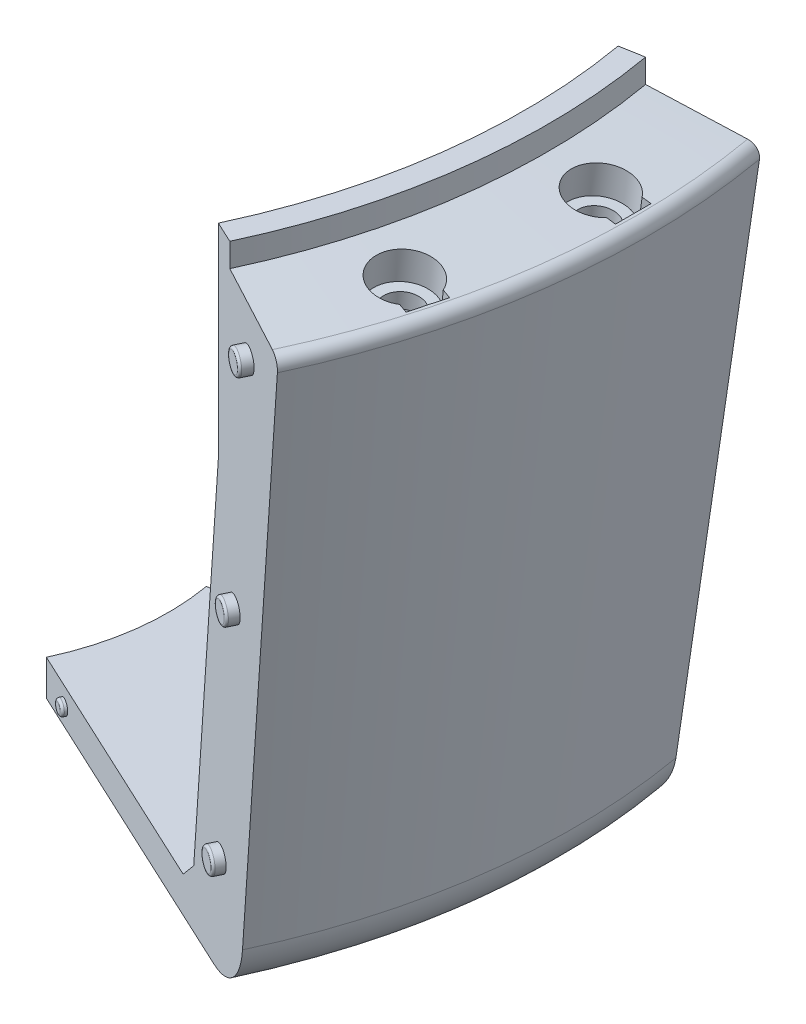
SolidWorks part; units mm, degrees
material "Melamine resin"
ref_plane "Front Plane" through (0, 0, 0) normal (0, 0, 1) x (1, 0, 0)
ref_plane "Top Plane" through (0, 0, 0) normal (0, 1, 0) x (1, 0, 0)
ref_plane "Right Plane" through (0, 0, 0) normal (1, 0, 0) x (0, 0, -1)
sketch "Sketch1" plane through (0, 0, 0) normal (0, 0, 1) x (1, 0, 0)
  line L0 (0, 0) -> (0, 30) construction
  line L3 (10, 0) -> (26.82, 0)
  line L4 (26.82, 0) -> (30.2136, 25.7776)
  line L5 (30.2136, 25.7776) -> (26, 26.3323)
  line L6 (26, 26.3323) -> (26, 27.3323)
  line L7 (26, 27.3323) -> (25, 27.3323)
  line L9 (22.9282, 3) -> (25, 18.7365)
  line L12 (25, 27.3323) -> (25, 18.7365)
  line L14 (21.4282, 3) -> (21.4282, 1.5)
  line L15 (21.4282, 1.5) -> (10, 1.5)
  line L16 (22.9282, 3) -> (21.4282, 3)
  line L17 (10, 1.5) -> (10, 0)
  dimension "D1" = 30
  dimension "D2" = 26
  dimension "D3" = 1
  dimension "D4" = 1.5
  dimension "D5" = 3
  dimension "D6" = 25
  dimension "D7" = 4.25
  dimension "D8" = 97.5
  dimension "D9" = 1
  dimension "D10" = 10
  dimension "D11" = 1.5
revolve "Revolve1" add sketch "Sketch1" angle 10 about L0
ref_plane "Plane1" through (3.8506, 29.2483, 0) normal (0.1305, 0.9914, 0) x (0.9914, -0.1305, 0)
sketch "Sketch2" plane through (3.8506, 29.2483, 0) normal (0.1305, 0.9914, 0) x (0.9914, -0.1305, 0)
  line L0 (25.8905, 0) -> (0, 0) construction
  line L1 (25.8905, -1.5732) -> (4, -1)
  line L2 (4, -1) -> (4, 1)
  line L3 (4, 1) -> (25.8905, 1.5732)
  line L4 (25.8905, 1.5732) -> (25.8905, -1.5732)
  line L5 (25.8905, 0) -> (26.4816, 0) construction
  ellipse E0 centre (-3.3646, 0) end of major axis (-3.3646, -30.2136) minor radius 29.9552 construction
  point P5 (26.5905, 0)
  point P8 (4, 0)
  dimension "D1" = 2
  dimension "D2" = 3
  dimension "D3" = 0.7
  dimension "D4" = 3.1464
  dimension "D5" = 4
extrude "Cut-Extrude1" cut sketch "Sketch2" against normal blind 19 from offset 2 offset against normal yes
pattern_circular "CirPattern1" count 2 every 15 about axis through (0, 0, 0) along (0, 1, 0) of "Cut-Extrude1"
sketch "Sketch3" plane through (3.8506, 29.2483, 0) normal (0.1305, 0.9914, 0) x (0.9914, -0.1305, 0)
  line L0 (0, 0) -> (27.8102, 0) construction
  circle A0 centre (24.5905, 0) radius 1.25
  ellipse E0 centre (-3.3646, 0) end of major axis (-3.3646, -30.2136) minor radius 29.9552 construction
  point P6 (26.5905, 0)
  dimension "D1" = 2.5
  dimension "D2" = 2
extrude "Cut-Extrude2" cut sketch "Sketch3" against normal blind 1.3
pattern_circular "CirPattern2" count 2 every 15 about axis through (0, 27.3323, 0) along (0, -1, 0) of "Cut-Extrude2"
sketch "Sketch4" plane through (3.6809, 27.9594, 0) normal (0.1305, 0.9914, 0) x (0.9914, -0.1305, 0)
  circle A0 centre (24.5905, 0) radius 0.75
  dimension "D1" = 1.5
extrude "Cut-Extrude3" cut sketch "Sketch4" against normal blind 19
pattern_circular "CirPattern3" count 2 every 15 about axis through (0, 27.3323, 0) along (0, -1, 0) of "Cut-Extrude3"
sketch "Sketch20" plane through (3.6809, 27.9594, 0) normal (0.1305, 0.9914, 0) x (0.9914, -0.1305, 0)
  circle A0 centre (24.5905, 0) radius 0.7
  dimension "D1" = 1.4
extrude "Cut-Extrude10" cut sketch "Sketch20" against normal blind 7.4 from offset 15 offset against normal yes
pattern_circular "CirPattern14" count 2 over 15 about axis through (0, 0, 0) along (0, -1, 0) of "Cut-Extrude10"
ref_plane "Plane2" through (26.363, -3.4708, 0.0001) normal (0.9914, -0.1305, 0) x (-0.012, -0.0914, -0.9957)
fillet "Fillet1" radius 2.5 1 edges at (26.5905, 0, 3.5007)
sketch "Sketch9" plane through (0, 27.3323, 0) normal (0, 1, 0) x (1, 0, 0)
  line L0 (0, 0) -> (29.8588, 0) construction
  line L19 (29.6, 0.75) -> (29, 0.75)
  line L20 (29.6, 0.75) -> (29.6, -0.75)
  line L21 (29.6, -0.75) -> (29, -0.75)
  line L22 (29, 0.75) -> (29, -0.75)
  point P9 (0, 0)
  dimension "D1" = 29
  dimension "D3" = 0.6
  dimension "D4" = 1.5
  dimension "D5" = 0.75
sketch "Sketch12" plane through (3.8506, 29.2483, 0) normal (0.1305, 0.9914, 0) x (0.9914, -0.1305, 0)
  circle A0 centre (24.5905, 0) radius 0.8
  dimension "D1" = 1.6
extrude "Cut-Extrude6" cut sketch "Sketch12" against normal blind 2
pattern_circular "CirPattern7" count 2 every 15 about axis through (0, 26.3323, 0) along (0, -1, 0) of "Cut-Extrude6"
fillet "Fillet5" radius 0.5 1 edges at (29.9552, 25.7776, 3.9437)
chamfer "Chamfer1" distance 2 angle 45 1 edges at (21.2449, 3, 2.7969)
extrude "Cut-Extrude13" cut sketch "Sketch9" against normal blind 2.7
pattern_circular "CirPattern15" count 2 every 15 about axis through (0, 0, 0) along (0, 1, 0) of "Cut-Extrude13"
sketch "Sketch21" plane through (0, 0, 0) normal (-0.1736, 0, -0.9848) x (-0.9848, 0, 0.1736)
  line L0 (-27.859, 26.0876) -> (-24.6275, 0) construction
  line L1 (-29.7179, 25.8428) -> (-26, 26.3323) construction
  circle A1 centre (-27.6131, 24.1027) radius 0.5
  circle A2 centre (-26.3944, 14.1773) radius 0.5
  circle A3 centre (-25.1757, 4.2518) radius 0.5
  circle A4 centre (-11.556, 0.7378) radius 0.3
  point P13 (0, 0)
  point P14 (0, 0)
  point P15 (0, 0)
  point P16 (0, 0)
  dimension "D1" = 2
  dimension "D2" = 3
extrude "Boss-Extrude1" add sketch "Sketch21" along normal blind 0.5
fillet "Fillet6" radius 0.1 4 edges at (24.214, 4.2518, -4.7773) (25.4142, 14.1773, -4.9889) (26.6144, 24.1027, -5.2005) (10.9982, 0.7378, -2.447)
pattern_circular "CirPattern16" count 2 every 36 about axis through (0, 0, 0) along (0, -1, 0) of "Boss-Extrude1"
fillet "Fillet7" radius 0.1 4 edges at (10.1168, 0.7378, 4.9343) (22.1784, 4.2518, 10.8171) (23.2737, 14.1773, 11.3514) (24.3691, 24.1027, 11.8856)
